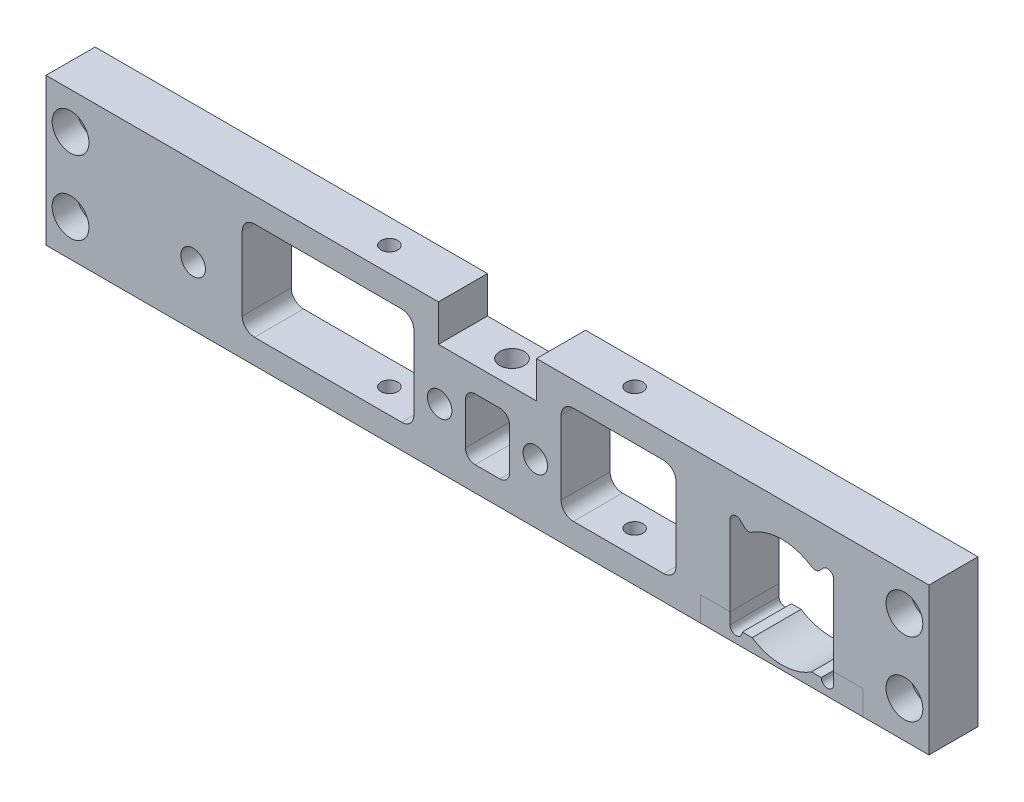
SolidWorks part; units mm, degrees
material "6061-T6 (SS)"
ref_plane "Front Plane" through (0, 0, 0) normal (0, 0, 1) x (1, 0, 0)
ref_plane "Top Plane" through (0, 0, 0) normal (0, 1, 0) x (1, 0, 0)
ref_plane "Right Plane" through (0, 0, 0) normal (1, 0, 0) x (0, 0, -1)
sketch "Sketch1" plane through (0, 0, 0) normal (0, 0, 1) x (1, 0, 0)
  line L1 (-190.5, -19.05) -> (38.1, -19.05)
  line L2 (-190.5, -19.05) -> (-190.5, 19.05)
  line L3 (-190.5, 19.05) -> (38.1, 19.05)
  line L4 (38.1, -19.05) -> (38.1, 19.05)
  line L5 (-190.5, -19.05) -> (38.1, 19.05) construction
  line L6 (-190.5, 19.05) -> (38.1, -19.05) construction
  line L7 (-190.5, 19.05) -> (38.1, 19.05)
  line L8 (-190.5, 19.05) -> (-190.5, -19.05)
  line L11 (-190.5, -19.05) -> (38.1, -19.05)
  line L12 (-190.5, -19.05) -> (-190.5, 19.05)
  line L15 (38.1, -19.05) -> (-190.5, -19.05)
  line L16 (38.1, -19.05) -> (38.1, 19.05)
  line L20 (38.1, -19.05) -> (38.1, 19.05)
  point P0 (0, 0)
  point P14 (-76.2, 0)
  dimension "D1" = 38.1
  dimension "D2" = 228.6
  dimension "D3" = 38.1
extrude "Boss-Extrude1" add sketch "Sketch1" along normal blind 12.7
sketch "Sketch5" plane through (0, 0, 12.7) normal (0, 0, 1) x (1, 0, 0)
  line L0 (0, -3.81) -> (11.8187, 8.0087) construction
  line L1 (0, -3.81) -> (11.8187, -3.81) construction
  line L2 (0, -3.81) -> (0, 8.0087) construction
  line L3 (0, 8.0087) -> (11.8187, 8.0087) construction
  line L4 (11.8187, -3.81) -> (11.8187, 8.0087) construction
  line L5 (-10.6872, 9.1402) -> (-8.7721, 7.2252)
  line L6 (0, -3.81) -> (11.8187, -3.81) construction
  line L7 (0, -3.81) -> (0, -15.6287) construction
  line L8 (0, -15.6287) -> (11.8187, -15.6287) construction
  line L9 (11.8187, -3.81) -> (11.8187, -15.6287) construction
  line L10 (0, -3.81) -> (-11.8187, -3.81) construction
  line L11 (0, -3.81) -> (0, -15.6287) construction
  line L12 (0, -15.6287) -> (-11.8187, -15.6287) construction
  line L13 (-11.8187, -3.81) -> (-11.8187, -15.6287) construction
  line L14 (0, -3.81) -> (-11.8187, -3.81) construction
  line L15 (0, -3.81) -> (0, 8.0087) construction
  line L16 (0, 8.0087) -> (-11.8187, 8.0087) construction
  line L17 (-11.8187, -3.81) -> (-11.8187, 8.0087) construction
  line L18 (-13.4189, 8.0087) -> (-13.4189, -15.6287)
  line L19 (13.4189, 8.0087) -> (13.4189, -15.6287)
  line L20 (10.9269, 9.3374) -> (8.7958, 7.2063)
  line L21 (-13.4189, -15.6287) -> (-13.4189, -19.05)
  line L22 (-190.5, -19.05) -> (38.1, -19.05) construction
  line L23 (-13.4189, -19.05) -> (13.4189, -19.05)
  line L24 (13.4189, -19.05) -> (13.4189, -15.6287)
  line L25 (-10.2185, -15.6287) -> (-7.6839, -15.6287)
  line L26 (10.2185, -15.6287) -> (7.6839, -15.6287)
  circle A0 centre (0, -3.81) radius 14.097 construction
  circle A1 centre (11.8187, 8.0087) radius 1.6002
  circle A2 centre (-11.8187, 8.0087) radius 1.6002
  circle A3 centre (-11.8187, -15.6287) radius 1.6002
  circle A4 centre (11.8187, -15.6287) radius 1.6002
  arc A5 (-8.7721, 7.2252) -> (8.7958, 7.2063) centre (0, -3.81) cw
  arc A6 (-7.6839, -15.6287) -> (7.6839, -15.6287) centre (0, -3.81) ccw
  point P6 (9.9681, 6.1581)
  point P7 (10.6872, 6.8772)
  line M8 (-190.5, -19.05) -> (38.1, -19.05)
  dimension "D1" = 28.194
  dimension "D2" = 3.2004
  dimension "D3" = 1.017
  dimension "D4" = 45
  dimension "D5" = 45
  dimension "D6" = 15.24
extrude "Cut-Extrude4" cut sketch "Sketch5" against normal through all contours A5 L5 A2 L18 A3 L21 L24 A4 L19 A1 L20 M8 | A4 | A3 | A2 | A1 L20
fillet "Fillet1" radius 1.5875 2 edges at (8.7958, 7.2063, 6.35) (-8.7721, 7.2252, 6.35)
sketch "Sketch6" plane through (0, 0, 12.7) normal (0, 0, 1) x (1, 0, 0)
  line L0 (-190.5, 19.05) -> (38.1, 19.05) construction
  line L1 (-88.9, 19.05) -> (-63.5, 19.05)
  line L2 (-88.9, 19.05) -> (-88.9, 9.525)
  line L3 (-88.9, 9.525) -> (-63.5, 9.525)
  line L4 (-63.5, 19.05) -> (-63.5, 9.525)
  point P6 (-76.2, 9.525)
  point P7 (-76.2, 19.05)
  point P8 (-88.9, 19.05)
  dimension "D1" = 9.525
  dimension "D2" = 25.4
  dimension "D3" = 0
extrude "Cut-Extrude5" cut sketch "Sketch6" against normal through all
sketch "Sketch7" plane through (0, 0, 12.7) normal (0, 0, 1) x (1, 0, 0)
  line L0 (-88.9, 9.525) -> (-63.5, 9.525) construction
  line L1 (-81.915, -12.7) -> (-70.485, -12.7)
  line L2 (-81.915, -12.7) -> (-81.915, 3.175)
  line L3 (-81.915, 3.175) -> (-70.485, 3.175)
  line L4 (-70.485, -12.7) -> (-70.485, 3.175)
  line L5 (-190.5, -19.05) -> (38.1, -19.05) construction
  point P4 (-76.2, 9.525)
  point P5 (-76.2, 3.175)
  dimension "D1" = 11.43
  dimension "D2" = 6.35
  dimension "D3" = 6.35
extrude "Cut-Extrude6" cut sketch "Sketch7" against normal through all
sketch "Sketch8" plane through (0, 9.525, 0) normal (0, 1, 0) x (1, 0, 0)
  line L0 (-88.9, 0) -> (-63.5, 0) construction
  line L1 (-88.9, -12.7) -> (-63.5, -12.7) construction
  circle A0 centre (-76.2, -6.35) radius 3.175
  point P2 (-76.2, 0)
  point P3 (-76.2, -12.7)
  dimension "D1" = 6.35
  dimension "D2" = 6.35
extrude "Cut-Extrude7" cut sketch "Sketch8" against normal up to surface (6.35 mm away) up to face at (-76.2, 3.175, 6.35)
sketch "Sketch9" plane through (0, 0, 0) normal (0, 0, -1) x (-1, 0, 0)
  line L0 (-38.1, -19.05) -> (-38.1, 19.05) construction
  line L1 (-31.75, 9.525) -> (184.15, 9.525) construction
  line L2 (-31.75, 9.525) -> (-31.75, -9.525) construction
  line L3 (-31.75, -9.525) -> (184.15, -9.525) construction
  line L4 (184.15, 9.525) -> (184.15, -9.525) construction
  line L5 (190.5, -19.05) -> (190.5, 19.05) construction
  line L6 (190.5, 19.05) -> (88.9, 19.05) construction
  line L7 (190.5, -19.05) -> (-38.1, -19.05) construction
  circle A0 centre (-31.75, 9.525) radius 3.175
  circle A1 centre (-31.75, -9.525) radius 3.175
  circle A2 centre (184.15, 9.525) radius 3.175
  circle A3 centre (184.15, -9.525) radius 3.175
  dimension "D2" = 6.35
  dimension "D3" = 6.35
  dimension "D1" = 6.35
  dimension "D4" = 9.525
  dimension "D5" = 9.525
extrude "Cut-Extrude8" cut sketch "Sketch9" against normal through all
sketch "Sketch10" plane through (0, 0, 12.7) normal (0, 0, 1) x (1, 0, 0)
  circle A0 centre (-184.15, 9.525) radius 4.7625
  circle A1 centre (-184.15, -9.525) radius 4.7625
  circle A2 centre (31.75, 9.525) radius 4.7625
  circle A3 centre (31.75, -9.525) radius 4.7625
  dimension "D1" = 9.525
extrude "Cut-Extrude9" cut sketch "Sketch10" against normal blind 6.35
fillet "Fillet2" radius 2.54 4 edges at (-81.915, 3.175, 6.35) (-70.485, 3.175, 6.35) (-70.485, -12.7, 6.35) (-81.915, -12.7, 6.35)
sketch "Sketch11" plane through (0, 0, 12.7) normal (0, 0, 1) x (1, 0, 0)
  line L0 (-21.0389, -19.05) -> (-21.0389, -12.7)
  line L1 (-190.5, -19.05) -> (38.1, -19.05) construction
  line L2 (-21.0389, -12.7) -> (21.0389, -12.7)
  line L3 (21.0389, -12.7) -> (21.0389, -19.05)
  line L4 (13.4189, 8.0087) -> (13.4189, -15.6287) construction
  line L5 (-13.4189, 8.0087) -> (-13.4189, -15.6287) construction
  dimension "D1" = 6.35
  dimension "D2" = 7.62
  dimension "D3" = 7.62
surface "Surface-Extrude1" sketch "Sketch11" parameters "D1"=12.7
split "Split1" trimming surface bodies 113 bodies to split 112 resulting bodies 114 115
sketch "Sketch12" plane through (0, -19.05, 0) normal (0, -1, 0) x (1, 0, 0)
  line L0 (-21.0389, 12.7) -> (21.0389, 12.7) construction
  line L1 (-21.0389, 0) -> (-21.0389, 12.7) construction
  line L2 (21.0389, 12.7) -> (21.0389, 0) construction
  circle A0 centre (-17.2289, 6.35) radius 1.4224
  circle A1 centre (17.2289, 6.35) radius 1.4224
  dimension "D1" = 2.8448
  dimension "D2" = 6.35
  dimension "D3" = 3.81
  dimension "D4" = 6.35
  dimension "D5" = 3.81
extrude "Cut-Extrude10" cut sketch "Sketch12" against normal blind 15.24
chamfer "Chamfer1" distance 2.1082 angle 41 1 edges at (18.6513, -19.05, 6.35) first distance on face at (17.2289, -12.7, 7.7724)
chamfer "Chamfer2" distance 2.1082 angle 41 1 edges at (-15.8065, -19.05, 6.35) first distance on face at (-17.2289, -12.7, 7.7724)
sketch "Sketch13" plane through (0, 0, 12.7) normal (0, 0, 1) x (1, 0, 0)
  line L0 (-21.0389, -12.7) -> (-21.0389, -19.05) construction
  line L1 (-57.15, -12.7) -> (-27.3889, -12.7)
  line L2 (-57.15, -12.7) -> (-57.15, 12.7)
  line L3 (-57.15, 12.7) -> (-27.3889, 12.7)
  line L4 (-27.3889, -12.7) -> (-27.3889, 12.7)
  line L5 (-63.5, 19.05) -> (38.1, 19.05) construction
  line L6 (-190.5, -19.05) -> (-21.0389, -19.05) construction
  line L7 (-63.5, 9.525) -> (-63.5, 19.05) construction
  line L8 (-190.5, 19.05) -> (-88.9, 19.05) construction
  line L9 (-95.25, 12.7) -> (-139.7, 12.7)
  line L10 (-95.25, 12.7) -> (-95.25, -12.7)
  line L11 (-95.25, -12.7) -> (-139.7, -12.7)
  line L12 (-139.7, 12.7) -> (-139.7, -12.7)
  line L13 (-88.9, 19.05) -> (-88.9, 9.525) construction
  dimension "D1" = 6.35
  dimension "D2" = 6.35
  dimension "D3" = 6.35
  dimension "D4" = 6.35
  dimension "D5" = 6.35
  dimension "D6" = 6.35
  dimension "D7" = 6.35
  dimension "D8" = 44.45
extrude "Cut-Extrude11" cut sketch "Sketch13" against normal through all
fillet "Fillet3" radius 3.175 8 edges at (-57.15, 12.7, 6.35) (-27.3889, -12.7, 6.35) (-27.3889, 12.7, 6.35) (-57.15, -12.7, 6.35) (-139.7, -12.7, 6.35) (-95.25, -12.7, 6.35) (-95.25, 12.7, 6.35) (-139.7, 12.7, 6.35)
sketch "Sketch14" plane through (0, 0, 12.7) normal (0, 0, 1) x (1, 0, 0)
  line L0 (0, -3.81) -> (38.1, -3.81) construction
  line L1 (38.1, -19.05) -> (38.1, 19.05) construction
  line L2 (-152.4, -3.81) -> (-190.5, -3.81) construction
  line L3 (-190.5, -19.05) -> (-190.5, 19.05) construction
  circle A0 centre (0, -3.81) radius 14.097 construction
  arc A1 (-7.6839, -15.6287) -> (7.6839, -15.6287) centre (0, -3.81) ccw construction
  circle A2 centre (-152.4, -3.81) radius 3.175
  dimension "D1" = 6.35
extrude "Cut-Extrude12" cut sketch "Sketch14" against normal through all
sketch "Sketch15" plane through (0, 0, 0) normal (0, 0, -1) x (-1, 0, 0)
  line L1 (155.6262, 1.778) -> (149.1738, 1.778) construction
  line L2 (149.1738, 1.778) -> (145.9475, -3.81) construction
  line L3 (145.9475, -3.81) -> (149.1738, -9.398) construction
  line L4 (149.1738, -9.398) -> (155.6262, -9.398) construction
  line L5 (155.6262, -9.398) -> (158.8525, -3.81) construction
  line L6 (158.8525, -3.81) -> (155.6262, 1.778) construction
  line L7 (145.6935, -9.398) -> (159.1065, -9.398)
  line L8 (145.6935, -9.398) -> (145.6935, 1.778)
  line L9 (145.6935, 1.778) -> (159.1065, 1.778)
  line L10 (159.1065, -9.398) -> (159.1065, 1.778)
  line L11 (145.6935, -9.398) -> (159.1065, 1.778) construction
  line L12 (145.6935, 1.778) -> (159.1065, -9.398) construction
  circle A0 centre (152.4, -3.81) radius 5.588 construction
  dimension "D1" = 11.176
  dimension "D2" = 0.254
extrude "Cut-Extrude13" cut sketch "Sketch15" against normal blind 4
fillet "Fillet4" radius 3.175 4 edges at (-159.1065, -9.398, 2) (-159.1065, 1.778, 2) (-145.6935, 1.778, 2) (-145.6935, -9.398, 2)
sketch "Sketch16" plane through (0, 0, 0) normal (0, 0, -1) x (-1, 0, 0)
  line L0 (190.5, -19.05) -> (21.0389, -19.05) construction
  line L1 (63.8175, -3.683) -> (57.15, -3.683) construction
  line L2 (57.15, 9.525) -> (57.15, -9.525) construction
  line L3 (88.5825, -3.683) -> (95.25, -3.683) construction
  line L4 (95.25, -9.525) -> (95.25, 9.525) construction
  line L5 (63.8175, -3.683) -> (70.485, -3.683) construction
  line L6 (70.485, -10.16) -> (70.485, 0.635) construction
  circle A0 centre (63.8175, -3.683) radius 3.175
  circle A1 centre (88.5825, -3.683) radius 3.175
  dimension "D2" = 6.35
  dimension "D1" = 15.367
extrude "Cut-Extrude14" cut sketch "Sketch16" against normal through all
sketch "Sketch17" plane through (0, 19.05, 0) normal (0, 1, 0) x (1, 0, 0)
  line L0 (-190.5, -12.7) -> (-190.5, 0) construction
  line L1 (-88.9, 0) -> (-88.9, -12.7) construction
  line L2 (-63.5, 0) -> (-63.5, -12.7) construction
  circle A0 centre (-107.95, -6.35) radius 2.159
  circle A1 centre (-44.45, -6.35) radius 2.159
  point P2 (-190.5, -6.35)
  point P7 (0, 0)
  dimension "D1" = 4.318
  dimension "D2" = 19.05
  dimension "D3" = 19.05
extrude "Cut-Extrude15" cut sketch "Sketch17" against normal through all
